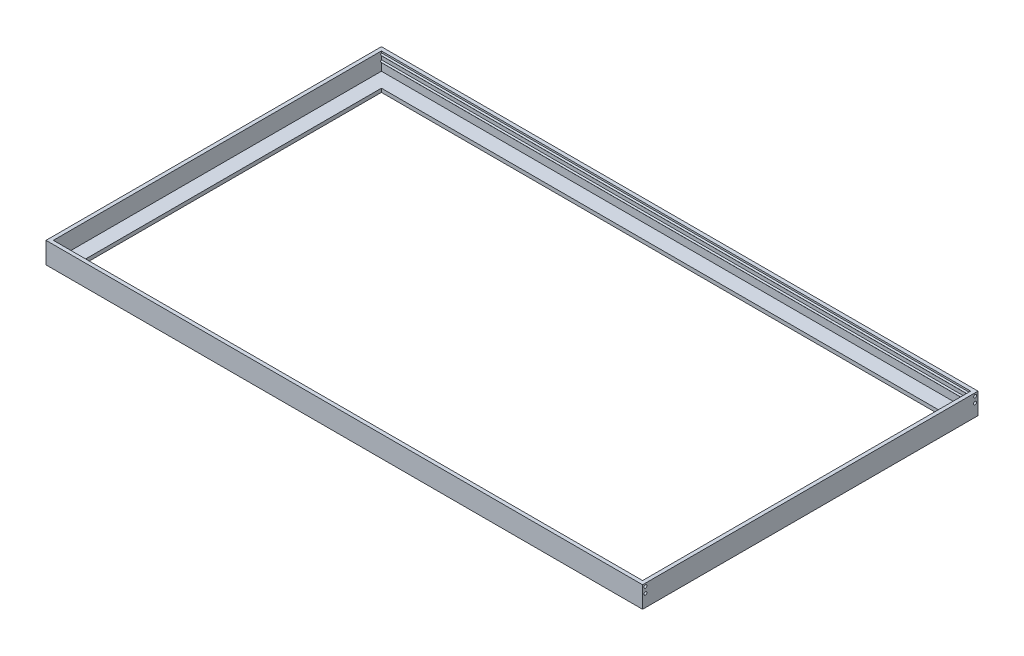
SolidWorks part; units mm, degrees
ref_plane "Front Plane" through (0, 0, 0) normal (0, 0, 1) x (1, 0, 0)
ref_plane "Top Plane" through (0, 0, 0) normal (0, 1, 0) x (1, 0, 0)
ref_plane "Right Plane" through (0, 0, 0) normal (1, 0, 0) x (0, 0, -1)
sketch "Sketch2" plane through (0, 0, 0) normal (0, 1, 0) x (1, 0, 0)
  line L1 (0, 0) -> (1626.4, 0)
  line L2 (0, 0) -> (0, 914.4)
  line L3 (0, 914.4) -> (1626.4, 914.4)
  line L4 (1626.4, 0) -> (1626.4, 914.4)
  dimension "D1" = 1626.4
  dimension "D2" = 914.4
extrude "Boss-Extrude1" add sketch "Sketch2" along normal blind 100
shell "Shell1" thickness 10 removed face at (813.2, 100, -457.2)
sketch "Sketch3" plane through (0, 10, 0) normal (0, 1, 0) x (1, 0, 0)
  line L0 (10, 904.4) -> (10, 10) construction
  line L1 (50, 864.4) -> (1576.4, 864.4)
  line L2 (50, 864.4) -> (50, 50)
  line L3 (50, 50) -> (1576.4, 50)
  line L4 (1576.4, 864.4) -> (1576.4, 50)
  line L5 (1616.4, 904.4) -> (10, 904.4) construction
  line L6 (1616.4, 10) -> (1616.4, 904.4) construction
  line L7 (10, 10) -> (1616.4, 10) construction
  dimension "D1" = 40
  dimension "D2" = 40
  dimension "D3" = 40
  dimension "D4" = 40
extrude "Cut-Extrude1" cut sketch "Sketch3" against normal through all
sketch "Sketch5" plane through (1626.4, 0, 0) normal (1, 0, 0) x (0, 0, -1)
  line L0 (0, 100) -> (0, 0) construction
  circle A0 centre (7.85, 50) radius 4
  dimension "D1" = 8
  dimension "D2" = 7.85
extrude "Cut-Extrude2" cut sketch "Sketch5" against normal through all
sketch "Sketch6" plane through (1626.4, 0, 0) normal (1, 0, 0) x (0, 0, -1)
  line L0 (0, 100) -> (0, 0) construction
  circle A0 centre (7.85, 66.28) radius 4
  circle A1 centre (7.85, 50) radius 4 construction
  dimension "D1" = 7.85
  dimension "D2" = 16.28
  dimension "D3" = 8
extrude "Cut-Extrude3" cut sketch "Sketch6" against normal through all
sketch "Sketch7" plane through (1626.4, 0, 0) normal (1, 0, 0) x (0, 0, -1)
  line L0 (0, 100) -> (0, 0) construction
  circle A0 centre (7.85, 33.72) radius 4
  circle A2 centre (7.85, 50) radius 4 construction
  dimension "D1" = 7.85
  dimension "D2" = 8
  dimension "D3" = 16.28
extrude "Cut-Extrude4" cut sketch "Sketch7" against normal through all
sketch "Sketch8" plane through (1626.4, 0, 0) normal (1, 0, 0) x (0, 0, -1)
  line L0 (914.4, 100) -> (914.4, 0) construction
  line L1 (0, 100) -> (914.4, 100)
  line L2 (0, 100) -> (0, 58)
  line L3 (0, 58) -> (914.4, 58)
  line L4 (914.4, 100) -> (914.4, 58)
  dimension "D1" = 42
extrude "Cut-Extrude5" cut sketch "Sketch8" against normal through all
sketch "Sketch9" plane through (1626.4, 0, 0) normal (1, 0, 0) x (0, 0, -1)
  line L2 (914.4, 58) -> (906.5, 58) construction
  line L3 (0, 58) -> (914.4, 58) construction
  line L4 (906.5, 58) -> (906.5, 50) construction
  line L5 (906.5, 50) -> (906.5, 33.7) construction
  circle A1 centre (906.5, 50) radius 4
  circle A2 centre (906.5, 33.7) radius 4
  dimension "D1" = 8
  dimension "D3" = 8
  dimension "D5" = 8
  dimension "D2" = 7.9
  dimension "D4" = 16.3
extrude "Cut-Extrude8" cut sketch "Sketch9" against normal through all
